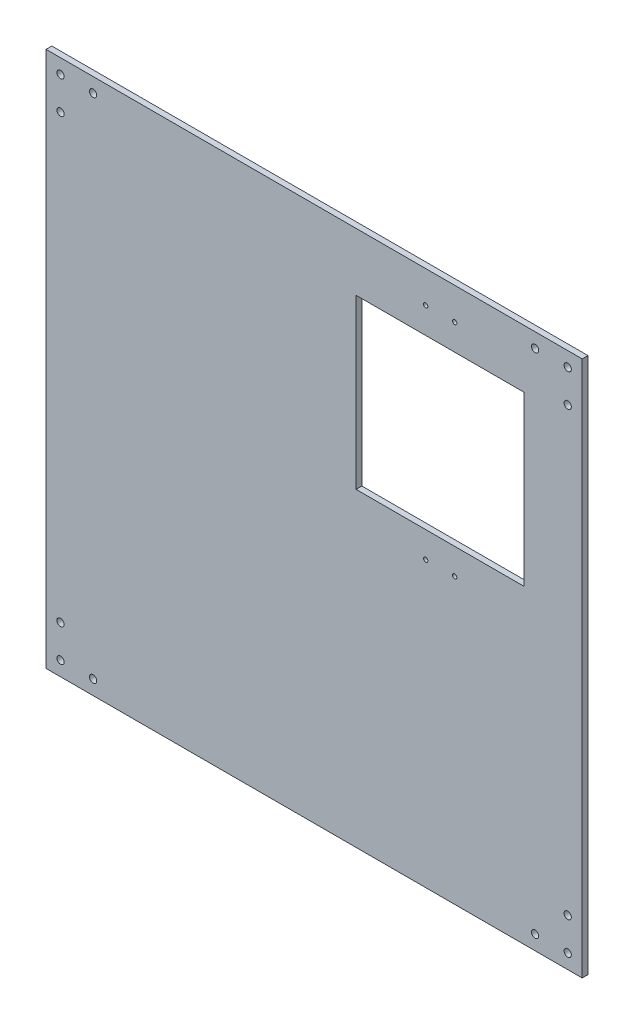
SolidWorks part; units mm, degrees
ref_plane "前视基准面" through (0, 0, 0) normal (0, 0, 1) x (1, 0, 0)
ref_plane "上视基准面" through (0, 0, 0) normal (0, 1, 0) x (1, 0, 0)
ref_plane "右视基准面" through (0, 0, 0) normal (1, 0, 0) x (0, 0, -1)
sketch "草图1" plane through (0, 0, 0) normal (0, 0, 1) x (1, 0, 0)
  line L1 (185, -185) -> (-185, -185)
  line L2 (185, -185) -> (185, 185)
  line L3 (185, 185) -> (-185, 185)
  line L4 (-185, -185) -> (-185, 185)
  line L5 (185, -185) -> (-185, 185) construction
  line L6 (185, 185) -> (-185, -185) construction
  point P0 (0, 0)
  dimension "D1" = 370
  dimension "D2" = 370
extrude "凸台-拉伸1" add sketch "草图1" along normal blind 4
sketch "草图2" plane through (0, 0, 4) normal (0, 0, 1) x (1, 0, 0)
  line L0 (-165, -175) -> (-152.5, -175) construction
  line L1 (-185, -185) -> (-165, -185) construction
  line L2 (-185, -185) -> (-185, -165) construction
  line L3 (-185, -165) -> (-165, -165) construction
  line L4 (-165, -185) -> (-165, -165) construction
  line L5 (-175, -165) -> (-175, -152.5) construction
  circle A0 centre (-175, -175) radius 2.5
  circle A1 centre (-152.5, -175) radius 2.5
  circle A2 centre (-175, -152.5) radius 2.5
  circle A3 centre (-152.5, 175) radius 2.5
  circle A4 centre (-175, 152.5) radius 2.5
  circle A5 centre (-175, 175) radius 2.5
  circle A6 centre (175, 152.5) radius 2.5
  circle A7 centre (152.5, 175) radius 2.5
  circle A8 centre (175, 175) radius 2.5
  circle A9 centre (152.5, -175) radius 2.5
  circle A10 centre (175, -152.5) radius 2.5
  circle A11 centre (175, -175) radius 2.5
  point P34 (0, 0)
  dimension "D3" = 10
  dimension "D4" = 10
  dimension "D5" = 5
  dimension "D6" = 12.5
  dimension "D7" = 5
  dimension "D9" = 5
  dimension "D1" = 20
  dimension "D2" = 20
  dimension "D8" = 12.5
  dimension "D10" = 4
extrude "切除-拉伸1" cut sketch "草图2" against normal through all
sketch "草图3" plane through (0, 0, 0) normal (0, 0, -1) x (-1, 0, 0)
  line L0 (-145, 29) -> (-145, 145)
  line L1 (-145, 145) -> (-29, 145)
  line L2 (-29, 145) -> (-29, 29)
  line L3 (-29, 29) -> (-145, 29)
extrude "切除-拉伸2" cut sketch "草图3" against normal blind 10
sketch "草图4" plane through (0, 0, 0) normal (0, 0, -1) x (-1, 0, 0)
  circle A0 centre (-97, 11) radius 1.5
  circle A1 centre (-77, 11) radius 1.5
  circle A2 centre (-97, 163) radius 1.5
  circle A3 centre (-77, 163) radius 1.5
extrude "切除-拉伸3" cut sketch "草图4" against normal blind 10
